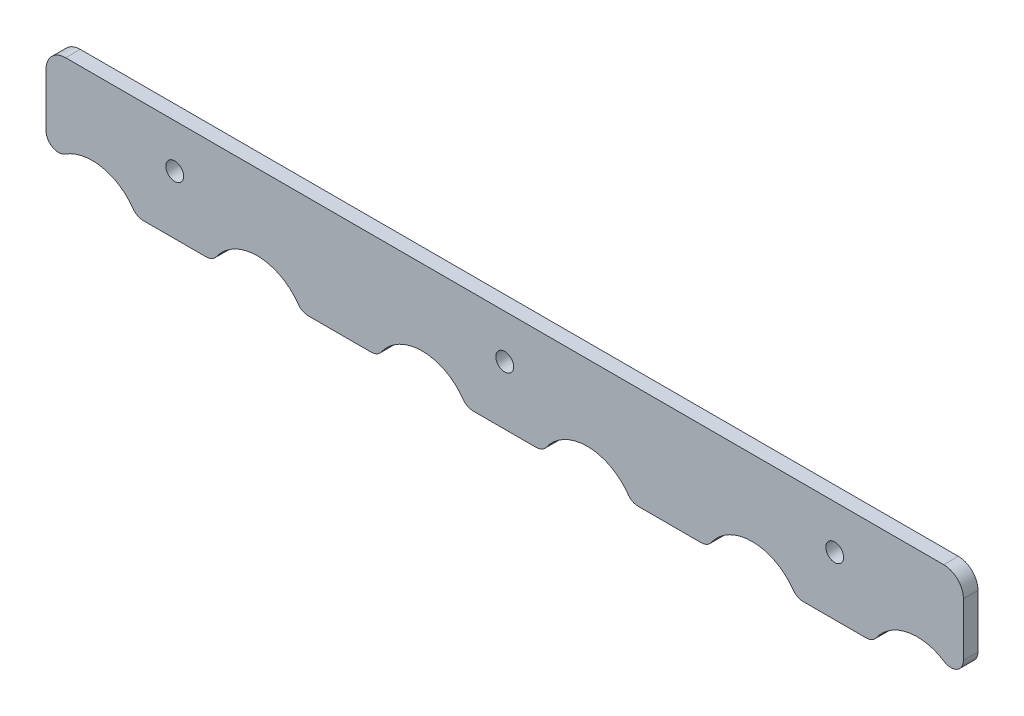
SolidWorks part; units mm, degrees
material "3003-H14"
ref_plane "X-Y Datum" through (0, 0, 0) normal (0, 0, 1) x (1, 0, 0)
ref_plane "X-Z Datum" through (0, 0, 0) normal (0, 1, 0) x (1, 0, 0)
ref_plane "Y-Z Datum" through (0, 0, 0) normal (1, 0, 0) x (0, 0, -1)
sketch "Sketch3" plane through (0, 0, 0) normal (0, 0, 1) x (1, 0, 0)
  line L1 (0, 0) -> (156.4633, 0) construction
  line L2 (0, 0) -> (0, 56.3098) construction
  line L3 (0, 56.3098) -> (156.4633, 56.3098) construction
  line L4 (156.4633, 0) -> (156.4633, 56.3098) construction
  line L5 (4.075, 10.775) -> (4.075, 28.535)
  line L6 (4.075, 28.535) -> (132.475, 28.535)
  line L7 (132.475, 28.535) -> (132.475, 10.775)
  line L9 (4.075, 13.775) -> (132.475, 13.775)
  line L10 (10.775, 10.775) -> (33.775, 10.775) construction
  line L11 (56.775, 10.775) -> (33.775, 10.775) construction
  line L48 (56.775, 10.775) -> (125.775, 10.775) construction
  circle A0 centre (10.775, 10.775) radius 10.775 construction
  circle A1 centre (33.775, 10.775) radius 10.775 construction
  circle A5 centre (56.775, 10.775) radius 10.775 construction
  circle A6 centre (10.775, 10.775) radius 4.7 construction
  circle A7 centre (33.775, 10.775) radius 4.7 construction
  circle A8 centre (56.775, 10.775) radius 4.7 construction
  circle A12 centre (79.775, 10.775) radius 10.775 construction
  circle A13 centre (79.775, 10.775) radius 4.7 construction
  circle A14 centre (102.775, 10.775) radius 10.775 construction
  circle A15 centre (102.775, 10.775) radius 4.7 construction
  circle A16 centre (125.775, 10.775) radius 10.775 construction
  circle A17 centre (125.775, 10.775) radius 4.7 construction
  circle A18 centre (125.775, 10.775) radius 10.775 construction
  circle A19 centre (102.775, 10.775) radius 10.775 construction
  circle A20 centre (79.775, 10.775) radius 10.775 construction
  circle A25 centre (10.775, 10.775) radius 6.7
  circle A26 centre (33.775, 10.775) radius 6.7
  circle A27 centre (56.775, 10.775) radius 6.7
  circle A28 centre (79.775, 10.775) radius 6.7
  circle A29 centre (102.775, 10.775) radius 6.7
  circle A30 centre (125.775, 10.775) radius 6.7
  dimension "D1" = 21.55
  dimension "D9" = 9.4
  dimension "D2" = 23
  dimension "D3" = 2
  dimension "D4" = 14.76
  dimension "D8" = 23
  dimension "D11" = 23
  dimension "D5" = 3
  dimension "D10" = 4
  dimension "D7" = 5
extrude "Boss-Extrude1" add sketch "Sketch3" along normal blind 2.032 contours A30 L9 L7 L6 L5 A25 A26 A27 A28 A29 | A25 L9 L5 | A30 L7 L9 region at (4.2857, 13.0332, 0) region at (68.275, 21.8085, 0) region at (132.2643, 13.0332, 0)
fillet "Fillet1" radius 3 2 edges at (4.075, 28.535, 1.016) (132.475, 28.535, 1.016)
fillet "Fillet2" radius 2 12 edges at (132.475, 10.775, 1.016) (119.7842, 13.775, 1.016) (108.7658, 13.775, 1.016) (96.7842, 13.775, 1.016) (85.7658, 13.775, 1.016) (73.7842, 13.775, 1.016) (62.7658, 13.775, 1.016) (50.7842, 13.775, 1.016) (39.7658, 13.775, 1.016) (27.7842, 13.775, 1.016) (16.7658, 13.775, 1.016) (4.075, 10.775, 1.016)
sketch "Sketch4" plane through (0, 0, 0) normal (0, 0, -1) x (-1, 0, 0)
  line L0 (-132.475, 22.185) -> (-4.075, 22.185) construction
  line L1 (-132.475, 25.535) -> (-132.475, 18.0962) construction
  line L2 (-4.075, 18.0962) -> (-4.075, 25.535) construction
  line L3 (-7.075, 28.535) -> (-129.475, 28.535) construction
  line L4 (-68.275, 28.535) -> (-68.275, 13.775) construction
  line L5 (-63.8947, 13.775) -> (-72.6553, 13.775) construction
  line L6 (-68.275, 22.185) -> (-4.075, 22.185) construction
  line L7 (-22.275, 13.775) -> (-22.275, 28.535) construction
  line L8 (-17.8947, 13.775) -> (-26.6553, 13.775) construction
  line L9 (-114.275, 13.775) -> (-114.275, 28.535) construction
  line L10 (-109.8947, 13.775) -> (-118.6553, 13.775) construction
  circle A0 centre (-22.275, 22.185) radius 1.2446
  circle A1 centre (-68.275, 22.185) radius 1.2446
  circle A3 centre (-114.275, 22.185) radius 1.2446
  point P30 (-68.275, 22.185)
  dimension "D1" = 2.4892
  dimension "D2" = 6.35
extrude "Cut-Extrude1" cut sketch "Sketch4" against normal through all
sketch "Sketch5" plane through (0, 0, 2.032) normal (0, 0, 1) x (1, 0, 0)
  line L0 (4.329, 25.535) -> (4.329, 18.0962)
  line L1 (17.8947, 14.029) -> (26.6553, 14.029)
  line L2 (40.8947, 14.029) -> (49.6553, 14.029)
  line L3 (63.8947, 14.029) -> (72.6553, 14.029)
  line L4 (86.8947, 14.029) -> (95.6553, 14.029)
  line L5 (109.8947, 14.029) -> (118.6553, 14.029)
  line L6 (132.221, 18.0962) -> (132.221, 25.535)
  line L7 (129.475, 28.281) -> (7.075, 28.281)
  line L8 (132.475, 18.0962) -> (132.475, 25.535)
  line L9 (129.475, 28.535) -> (7.075, 28.535)
  line L10 (4.075, 25.535) -> (4.075, 18.0962)
  line L11 (17.8947, 13.775) -> (26.6553, 13.775)
  line L12 (40.8947, 13.775) -> (49.6553, 13.775)
  line L13 (63.8947, 13.775) -> (72.6553, 13.775)
  line L14 (86.8947, 13.775) -> (95.6553, 13.775)
  line L15 (109.8947, 13.775) -> (118.6553, 13.775)
  line L16 (132.475, 18.0962) -> (132.475, 25.535)
  line L17 (129.475, 28.535) -> (7.075, 28.535)
  line L18 (4.075, 25.535) -> (4.075, 18.0962)
  line L19 (17.8947, 13.775) -> (26.6553, 13.775)
  line L20 (40.8947, 13.775) -> (49.6553, 13.775)
  line L21 (63.8947, 13.775) -> (72.6553, 13.775)
  line L22 (86.8947, 13.775) -> (95.6553, 13.775)
  line L23 (109.8947, 13.775) -> (118.6553, 13.775)
  arc A0 (4.329, 18.0962) -> (7.0182, 16.6269) centre (6.075, 18.0962) ccw
  arc A1 (16.4658, 14.7716) -> (7.0182, 16.6269) centre (10.775, 10.775) ccw
  arc A2 (16.4658, 14.7716) -> (17.8947, 14.029) centre (17.8947, 15.775) ccw
  arc A3 (26.6553, 14.029) -> (28.0842, 14.7716) centre (26.6553, 15.775) ccw
  arc A4 (39.4658, 14.7716) -> (28.0842, 14.7716) centre (33.775, 10.775) ccw
  arc A5 (39.4658, 14.7716) -> (40.8947, 14.029) centre (40.8947, 15.775) ccw
  arc A6 (49.6553, 14.029) -> (51.0842, 14.7716) centre (49.6553, 15.775) ccw
  arc A7 (62.4658, 14.7716) -> (51.0842, 14.7716) centre (56.775, 10.775) ccw
  arc A8 (62.4658, 14.7716) -> (63.8947, 14.029) centre (63.8947, 15.775) ccw
  arc A9 (72.6553, 14.029) -> (74.0842, 14.7716) centre (72.6553, 15.775) ccw
  arc A10 (85.4658, 14.7716) -> (74.0842, 14.7716) centre (79.775, 10.775) ccw
  arc A11 (85.4658, 14.7716) -> (86.8947, 14.029) centre (86.8947, 15.775) ccw
  arc A12 (95.6553, 14.029) -> (97.0842, 14.7716) centre (95.6553, 15.775) ccw
  arc A13 (108.4658, 14.7716) -> (97.0842, 14.7716) centre (102.775, 10.775) ccw
  arc A14 (108.4658, 14.7716) -> (109.8947, 14.029) centre (109.8947, 15.775) ccw
  arc A15 (118.6553, 14.029) -> (120.0842, 14.7716) centre (118.6553, 15.775) ccw
  arc A16 (129.5318, 16.6269) -> (120.0842, 14.7716) centre (125.775, 10.775) ccw
  arc A17 (129.5318, 16.6269) -> (132.221, 18.0962) centre (130.475, 18.0962) ccw
  arc A18 (132.221, 25.535) -> (129.475, 28.281) centre (129.475, 25.535) ccw
  arc A19 (7.075, 28.281) -> (4.329, 25.535) centre (7.075, 25.535) ccw
  arc A20 (129.3945, 16.4132) -> (120.292, 14.6256) centre (125.775, 10.775) ccw
  arc A21 (129.3945, 16.4132) -> (132.475, 18.0962) centre (130.475, 18.0962) ccw
  arc A22 (132.475, 25.535) -> (129.475, 28.535) centre (129.475, 25.535) ccw
  arc A23 (7.075, 28.535) -> (4.075, 25.535) centre (7.075, 25.535) ccw
  arc A24 (4.075, 18.0962) -> (7.1555, 16.4132) centre (6.075, 18.0962) ccw
  arc A25 (16.258, 14.6256) -> (7.1555, 16.4132) centre (10.775, 10.775) ccw
  arc A26 (16.258, 14.6256) -> (17.8947, 13.775) centre (17.8947, 15.775) ccw
  arc A27 (26.6553, 13.775) -> (28.292, 14.6256) centre (26.6553, 15.775) ccw
  arc A28 (39.258, 14.6256) -> (28.292, 14.6256) centre (33.775, 10.775) ccw
  arc A29 (39.258, 14.6256) -> (40.8947, 13.775) centre (40.8947, 15.775) ccw
  arc A30 (49.6553, 13.775) -> (51.292, 14.6256) centre (49.6553, 15.775) ccw
  arc A31 (62.258, 14.6256) -> (51.292, 14.6256) centre (56.775, 10.775) ccw
  arc A32 (62.258, 14.6256) -> (63.8947, 13.775) centre (63.8947, 15.775) ccw
  arc A33 (72.6553, 13.775) -> (74.292, 14.6256) centre (72.6553, 15.775) ccw
  arc A34 (85.258, 14.6256) -> (74.292, 14.6256) centre (79.775, 10.775) ccw
  arc A35 (85.258, 14.6256) -> (86.8947, 13.775) centre (86.8947, 15.775) ccw
  arc A36 (95.6553, 13.775) -> (97.292, 14.6256) centre (95.6553, 15.775) ccw
  arc A37 (108.258, 14.6256) -> (97.292, 14.6256) centre (102.775, 10.775) ccw
  arc A38 (108.258, 14.6256) -> (109.8947, 13.775) centre (109.8947, 15.775) ccw
  arc A39 (118.6553, 13.775) -> (120.292, 14.6256) centre (118.6553, 15.775) ccw
  arc A40 (129.3945, 16.4132) -> (120.292, 14.6256) centre (125.775, 10.775) ccw
  arc A41 (129.3945, 16.4132) -> (132.475, 18.0962) centre (130.475, 18.0962) ccw
  arc A42 (132.475, 25.535) -> (129.475, 28.535) centre (129.475, 25.535) ccw
  arc A43 (7.075, 28.535) -> (4.075, 25.535) centre (7.075, 25.535) ccw
  arc A44 (4.075, 18.0962) -> (7.1555, 16.4132) centre (6.075, 18.0962) ccw
  arc A45 (16.258, 14.6256) -> (7.1555, 16.4132) centre (10.775, 10.775) ccw
  arc A46 (16.258, 14.6256) -> (17.8947, 13.775) centre (17.8947, 15.775) ccw
  arc A47 (26.6553, 13.775) -> (28.292, 14.6256) centre (26.6553, 15.775) ccw
  arc A48 (39.258, 14.6256) -> (28.292, 14.6256) centre (33.775, 10.775) ccw
  arc A49 (39.258, 14.6256) -> (40.8947, 13.775) centre (40.8947, 15.775) ccw
  arc A50 (49.6553, 13.775) -> (51.292, 14.6256) centre (49.6553, 15.775) ccw
  arc A51 (62.258, 14.6256) -> (51.292, 14.6256) centre (56.775, 10.775) ccw
  arc A52 (62.258, 14.6256) -> (63.8947, 13.775) centre (63.8947, 15.775) ccw
  arc A53 (72.6553, 13.775) -> (74.292, 14.6256) centre (72.6553, 15.775) ccw
  arc A54 (85.258, 14.6256) -> (74.292, 14.6256) centre (79.775, 10.775) ccw
  arc A55 (85.258, 14.6256) -> (86.8947, 13.775) centre (86.8947, 15.775) ccw
  arc A56 (95.6553, 13.775) -> (97.292, 14.6256) centre (95.6553, 15.775) ccw
  arc A57 (108.258, 14.6256) -> (97.292, 14.6256) centre (102.775, 10.775) ccw
  arc A58 (108.258, 14.6256) -> (109.8947, 13.775) centre (109.8947, 15.775) ccw
  arc A59 (118.6553, 13.775) -> (120.292, 14.6256) centre (118.6553, 15.775) ccw
  dimension "D1" = 0
  dimension "D2" = 0.254
extrude "Cut-Extrude2" cut sketch "Sketch5" against normal through all
